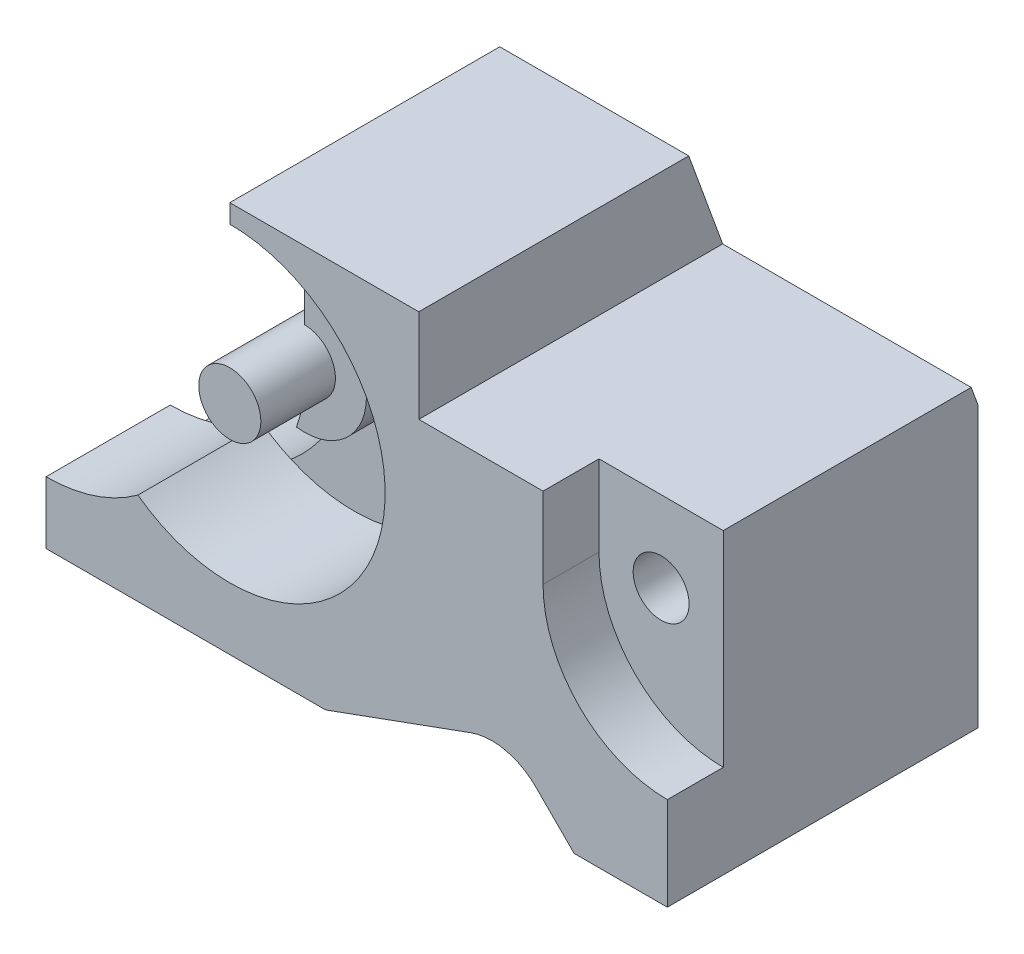
SolidWorks part; units mm, degrees
ref_plane "Front Plane" through (0, 0, 0) normal (0, 0, 1) x (1, 0, 0)
ref_plane "Top Plane" through (0, 0, 0) normal (0, 1, 0) x (1, 0, 0)
ref_plane "Right Plane" through (0, 0, 0) normal (1, 0, 0) x (0, 0, -1)
sketch "Sketch1" plane through (0, 0, 0) normal (0, 0, 1) x (1, 0, 0)
  line L0 (60, 48) -> (100, 48)
  line L1 (0, 0) -> (45, 0)
  line L2 (0, 0) -> (0, 10)
  line L3 (0, 63) -> (29.5804, 63) construction
  line L4 (60, 48) -> (60, 63)
  line L5 (100, 48) -> (100, 0)
  line L6 (100, 0) -> (85, 0)
  line L7 (85, 0) -> (78.8309, 6.1691)
  line L8 (45, 0) -> (68.3397, 8.4949)
  line L9 (80, 48) -> (80, 35)
  line L10 (29.5804, 35) -> (0, 35) construction
  line L11 (29.5804, 40) -> (29.5804, 60)
  line L14 (54.5404, 63) -> (60, 63)
  line L15 (29.5804, 60) -> (29.5804, 63)
  line L16 (29.5804, 63) -> (54.5404, 63)
  line L17 (0, 10) -> (0, 63) construction
  line L18 (80, 35) -> (90, 35) construction
  line L19 (90, 35) -> (100, 35) construction
  circle A4 centre (29.5804, 35) radius 5
  arc A6 (68.3397, 8.4949) -> (78.8309, 6.1691) centre (71.7599, -0.902) cw
  arc A7 (0, 10) -> (14.7902, 14.8444) centre (0, 35) ccw
  arc A8 (14.7902, 14.8444) -> (29.5804, 60) centre (29.5804, 35) ccw
  arc A9 (29.5804, 30) -> (19.4385, 12.1496) centre (0, 35) cw
  arc A10 (28.3127, 25.0807) -> (29.5804, 45) centre (29.5804, 35) ccw
  arc A11 (80, 35) -> (100, 15) centre (100, 35) ccw
  circle A12 centre (90, 35) radius 4.5
  dimension "D1" = 63
  dimension "D2" = 10
  dimension "D3" = 25
  dimension "D5" = 50
  dimension "D13" = 10
  dimension "D15" = 30
  dimension "D16" = 20
  dimension "D19" = 20
  dimension "D21" = 9
  dimension "D4" = 35
  dimension "D6" = 60
  dimension "D7" = 15
  dimension "D8" = 40
  dimension "D9" = 15
  dimension "D10" = 45
  dimension "D11" = 40
  dimension "D12" = 20
  dimension "D14" = 20
  dimension "D20" = 35
  dimension "D22" = 10
extrude "Boss-Extrude1" add sketch "Sketch1" along normal blind 50 contours A11 L9 L0 L4 L14 L16 L15 A8 A7 L2 L1 L8 A6 L7 L6 L5 | A4 region at (57.485, 22.4684, 0) region at (29.5804, 35, 0)
extrude "Boss-Extrude2" add sketch "Sketch1<5>" along normal blind 41 contours L9 A11 L5 A12 region at (90, 47.6141, 0)
sketch "Sketch1<5>" plane through (0, 0, 0) normal (0, 0, 1) x (1, 0, 0) same geometry as "Sketch1"
extrude "Boss-Extrude3" add sketch "Sketch1<6>" along normal blind 30 contours A10 A9 A8 L11 region at (40.1112, 33.34, 0)
sketch "Sketch1<6>" plane through (0, 0, 0) normal (0, 0, 1) x (1, 0, 0) same geometry as "Sketch1"
extrude "Boss-Extrude4" add sketch "Sketch1<7>" along normal blind 38 contours A9 A10 L11 A4 region at (39.3311, 34.3794, 0)
sketch "Sketch1<7>" plane through (0, 0, 0) normal (0, 0, 1) x (1, 0, 0) same geometry as "Sketch1"
sketch "Sketch4" plane through (0, 0, 0) normal (0, 0, 1) x (1, 0, 0)
  line L0 (0, 10) -> (0, 35)
  line L1 (24.5804, 35) -> (0, 35)
  line L2 (0, 0) -> (0, 10) construction
  line L4 (0, 10) -> (0, 5)
  line L5 (24.5804, 35) -> (29.5804, 35) construction
  arc A0 (29.5804, 30) -> (0, 5) centre (0, 35) cw
  arc A4 (24.5804, 35) -> (29.5804, 30) centre (29.5804, 35) ccw
  circle A5 centre (29.5804, 35) radius 5 construction
extrude "Cut-Extrude1" cut sketch "Sketch4" along normal blind 30
sketch "Sketch5" plane through (60, 0, 0) normal (1, 0, 0) x (0, 0, -1)
  line L0 (0, 45) -> (-6.5515, 63)
  line L1 (0, 48) -> (0, 0) construction
  line L2 (-50, 63) -> (0, 63) construction
  line L3 (0, 48) -> (0, 63) construction
  line L4 (-6.5515, 63) -> (0, 63)
  line L5 (0, 63) -> (0, 45)
  dimension "D1" = 20
  dimension "D2" = 18
extrude "Cut-Extrude2" cut sketch "Sketch5" against normal through all both and the other way through all
